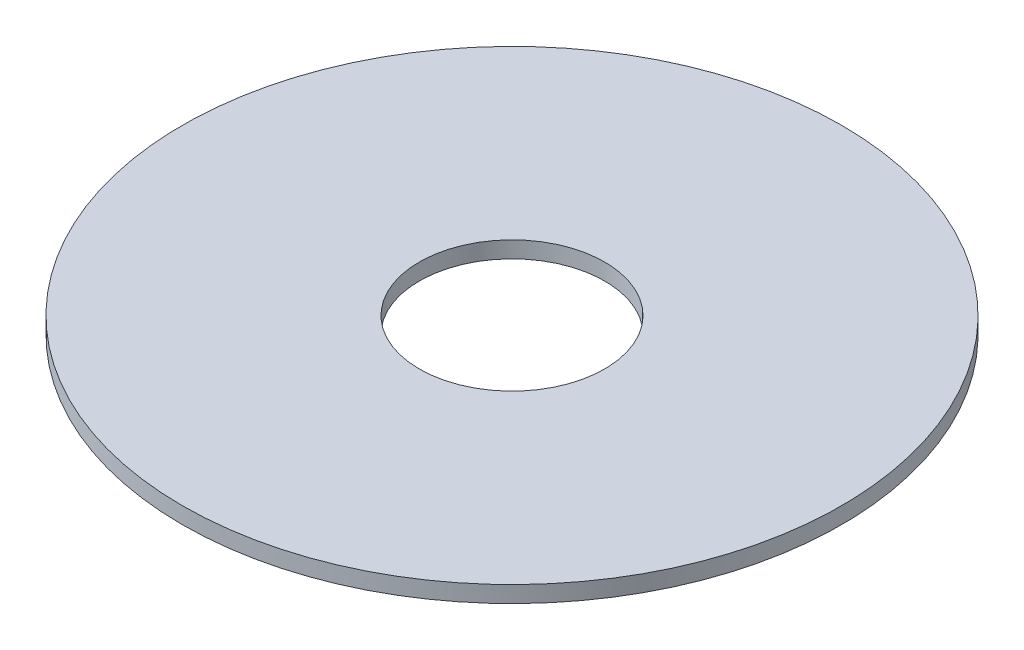
SolidWorks part; units mm, degrees
ref_plane "Front Plane" through (0, 0, 0) normal (0, 0, 1) x (1, 0, 0)
ref_plane "Top Plane" through (0, 0, 0) normal (0, 1, 0) x (1, 0, 0)
ref_plane "Right Plane" through (0, 0, 0) normal (1, 0, 0) x (0, 0, -1)
sketch "Sketch1" plane through (0, 0, 0) normal (0, 1, 0) x (1, 0, 0)
  circle A0 centre (0, 0) radius 80
  dimension "FLANGE_OD" = 160
extrude "Boss-Extrude1" add sketch "Sketch1" along normal blind 4
sketch "Sketch2" plane through (0, 0, 0) normal (0, 1, 0) x (1, 0, 0)
  circle A0 centre (0, 0) radius 22.5
  dimension "BORE_D" = 45
extrude "Cut-Extrude1" cut sketch "Sketch2" along normal through all
sketch "Sketch3" plane through (0, 4, 0) normal (0, 1, 0) x (1, 0, 0)
  circle A0 centre (0, 0) radius 15.4836 construction
  circle A1 centre (-15.4836, 0) radius 6.7184
  dimension "BOLT_D" = 13.4368
  dimension "BOLT_PCD" = 30.9673
extrude "Cut-Extrude2" cut sketch "Sketch3" against normal blind 2.5627 rebuild error yes
pattern_circular "CirPattern1" count 4 over 360 rebuild error yes
